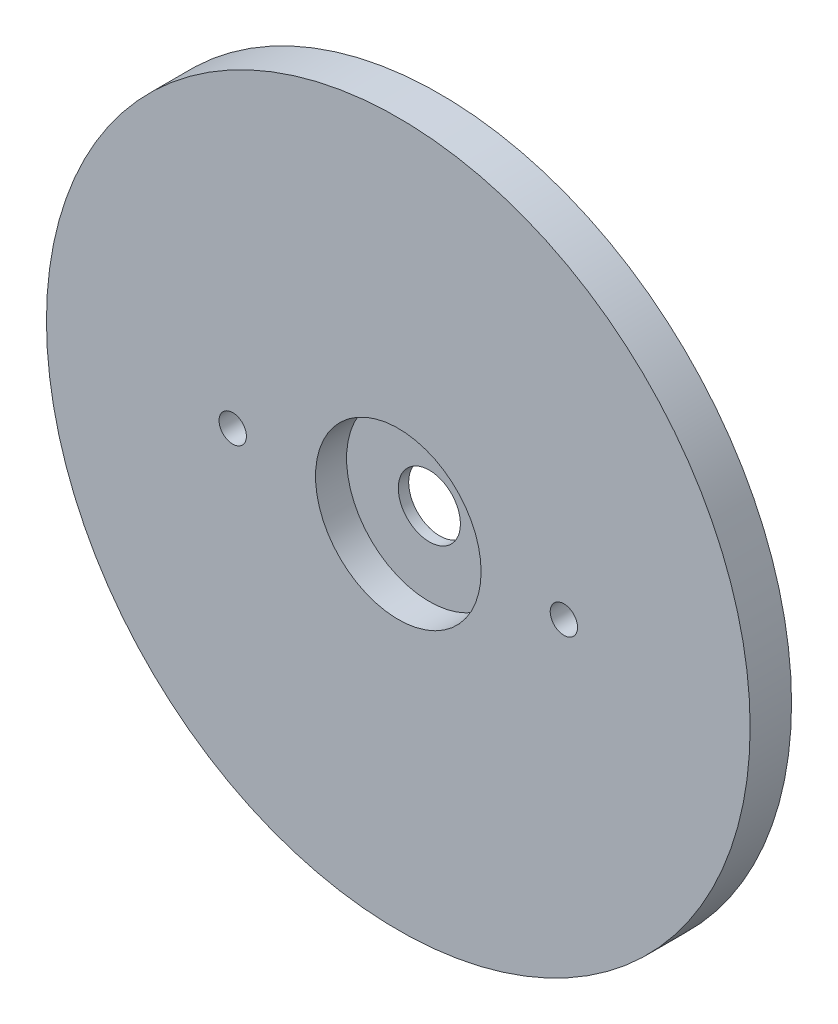
SolidWorks part; units mm, degrees
ref_plane "Front Plane" through (0, 0, 0) normal (0, 0, 1) x (1, 0, 0)
ref_plane "Top Plane" through (0, 0, 0) normal (0, 1, 0) x (1, 0, 0)
ref_plane "Right Plane" through (0, 0, 0) normal (1, 0, 0) x (0, 0, -1)
sketch "Sketch1" plane through (0, 0, 0) normal (0, 0, 1) x (1, 0, 0)
  circle A0 centre (0, 0) radius 85
  dimension "D1" = 170
extrude "Boss-Extrude1" add sketch "Sketch1" along normal blind 10
sketch "Sketch2" plane through (0, 0, 10) normal (0, 0, 1) x (1, 0, 0)
  circle A0 centre (0, 0) radius 20
  dimension "D1" = 40
extrude "Cut-Extrude1" cut sketch "Sketch2" against normal blind 7.5
sketch "Sketch3" plane through (0, 0, 0) normal (0, 0, -1) x (-1, 0, 0)
  circle A0 centre (0, 0) radius 7.5
  dimension "D1" = 15
extrude "Cut-Extrude2" cut sketch "Sketch3" against normal blind 20
sketch "Sketch4" plane through (0, 0, 10) normal (0, 0, 1) x (1, 0, 0)
  line L0 (0, 85) -> (0, -85) construction
  line L1 (40, 0) -> (-40, 0) construction
  circle A0 centre (0, 0) radius 85 construction
  circle A1 centre (-40, 0) radius 3.3
  circle A2 centre (40, 0) radius 3.3
  point P9 (0, 0)
  dimension "D2" = 6.6
  dimension "D1" = 40
extrude "Cut-Extrude3" cut sketch "Sketch4" against normal through all both and the other way through all
